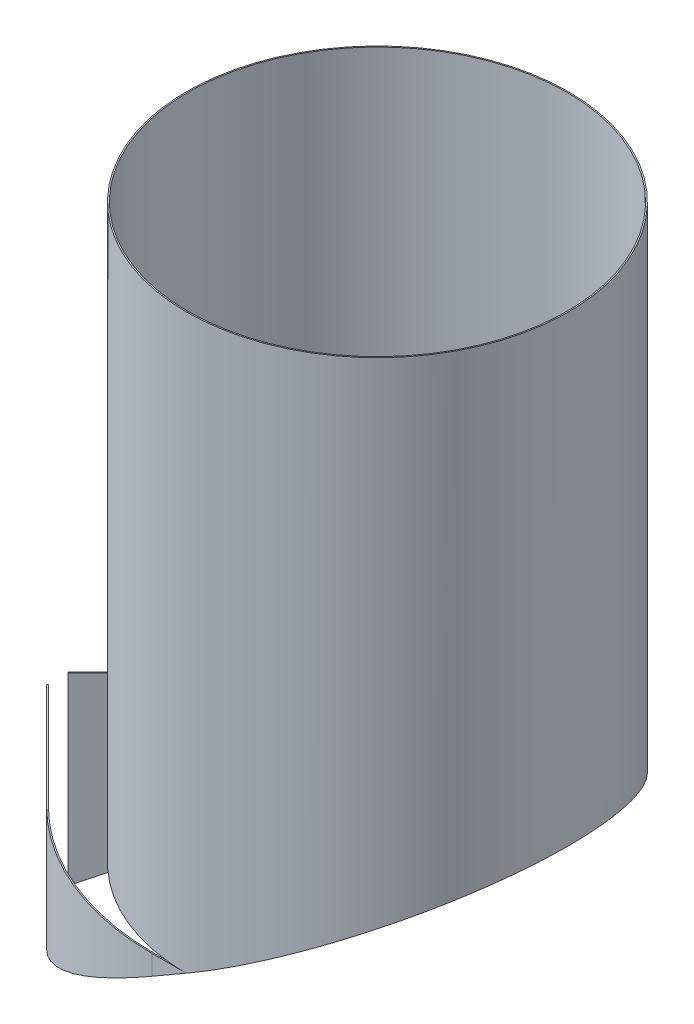
SolidWorks part; units mm, degrees
ref_plane "Front Plane" through (0, 0, 0) normal (0, 0, 1) x (1, 0, 0)
ref_plane "Top Plane" through (0, 0, 0) normal (0, 1, 0) x (1, 0, 0)
ref_plane "Right Plane" through (0, 0, 0) normal (1, 0, 0) x (0, 0, -1)
sketch "Sketch1" plane through (0, 0, 0) normal (0, 1, 0) x (1, 0, 0)
  line L0 (-55, 0) -> (55, 0) construction
  line L1 (0, 0) -> (323.9878, 323.9878) construction
  line L2 (0, 0) -> (323.9878, -323.9878) construction
  line L3 (8.4853, -8.4853) -> (150, -150)
  line L4 (150, -150) -> (260, -150)
  line L5 (150, 150) -> (260, 150)
  line L6 (8.4853, 8.4853) -> (150, 150)
  arc A0 (8.4853, -8.4853) -> (8.4853, 8.4853) centre (0, 0) ccw
  circle A1 centre (0, 0) radius 12 construction
  circle A2 centre (0, 0) radius 110 construction
  arc A3 (260, -150) -> (260, 150) centre (260, 0) ccw
  point P1 (0, 0)
  dimension "D1" = 24
  dimension "D2" = 24
  dimension "D3" = 220
  dimension "D4" = 300
  dimension "D5" = 45
extrude "Boss-Extrude1" add sketch "Sketch1" along normal blind 600
sketch "Sketch2" plane through (0, 0, 0) normal (0, 0, 1) x (1, 0, 0)
  line L0 (0, 0) -> (410, 236.7136)
  line L1 (410, 236.7136) -> (410, 0)
  line L2 (410, 0) -> (0, 0)
  line L3 (260, 0) -> (410, 0) construction
  line L4 (55, 0) -> (-55, 0) construction
  point P6 (0, 0)
  point P7 (0, 0)
  point P8 (0, 0)
  point P9 (0, 0)
  dimension "D1" = 30
extrude "Cut-Extrude1" cut sketch "Sketch2" against normal through all both and the other way through all
sketch "Sketch3" plane through (0, 600, 0) normal (0, 1, 0) x (1, 0, 0)
  line L0 (0, 0) -> (150, 150)
  line L1 (0, 0) -> (150, -150)
  line L2 (150, -150) -> (260, -150)
  line L4 (-55, 0) -> (55, 0) construction
  line L5 (150, 150) -> (260, 150)
  arc A0 (260, 150) -> (260, -150) centre (260, 0) ccw
extrude "Cut-Extrude2" cut sketch "Sketch3" along direction (0, 1, 0) on the side against the normal blind 450
fillet "Fillet1" radius 200 2 edges at (150, 118.3013, 150) (150, 118.3013, -150)
shell "Shell2" thickness 1 removed face at (150.4927, 86.887, 18.75) removed face at (10.2426, 77.9568, 0) removed face at (147.1221, 150, 18.75) removed face at (260, 600, 150)
